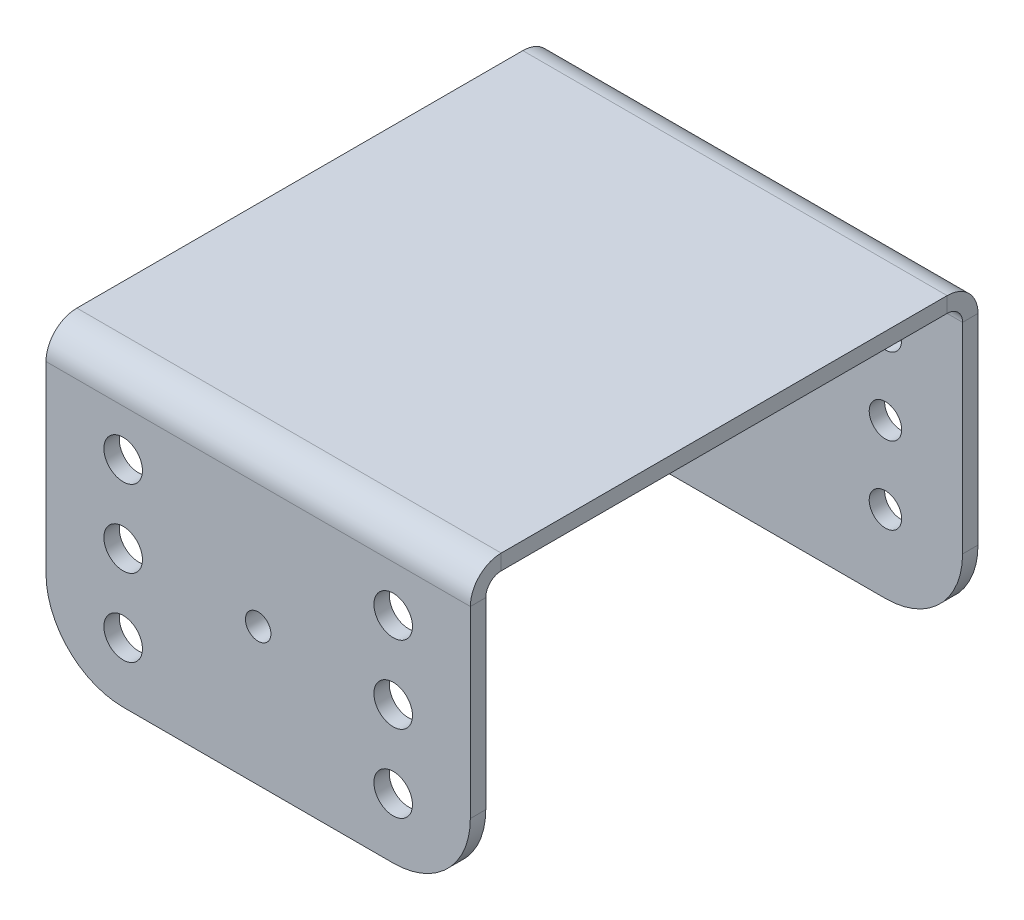
SolidWorks part; units mm, degrees
note: The reader was unsure of these and kept them because the rebuilt part matched: flange length of "边线-法兰1", "边线-法兰2".
material "1023 碳钢板 (SS)"
ref_plane "前视基准面" through (0, 0, 0) normal (0, 0, 1) x (1, 0, 0)
ref_plane "上视基准面" through (0, 0, 0) normal (0, 1, 0) x (1, 0, 0)
ref_plane "右视基准面" through (0, 0, 0) normal (1, 0, 0) x (0, 0, -1)
sketch "草图1" plane through (0, 0, 0) normal (0, 0, 1) x (1, 0, 0)
  line L0 (0, 0) -> (25062.9318, 0) construction
  line L1 (0, 0) -> (0, 25062.9318) construction
  line L3 (-27.5, 20) -> (27.5, 20)
  line L4 (-27.5, 20) -> (-27.5, -10)
  line L5 (-17.5, -20) -> (17.5, -20)
  line L6 (27.5, 20) -> (27.5, -10)
  circle A0 centre (-17.5, 10) radius 2.1
  circle A1 centre (17.5, 10) radius 2.1
  circle A2 centre (17.5, -10) radius 2.1
  circle A3 centre (-17.5, -10) radius 2.1
  arc A4 (-27.5, -10) -> (-17.5, -20) centre (-17.5, -10) ccw
  arc A5 (17.5, -20) -> (27.5, -10) centre (17.5, -10) ccw
  circle A6 centre (-17.5, 0) radius 2.1
  circle A7 centre (17.5, 0) radius 2.1
  point P19 (-27.5, -20)
  dimension "D3" = 4.2
  dimension "D4" = 10
  dimension "D5" = 10
  dimension "D6" = 10
  dimension "D7" = 4.2
  dimension "D1" = 40
  dimension "D2" = 55
base flange "基体-法兰1" sketch "草图1" thickness 2 reverse thickness direction no parameters "D1"=2
edge flange "边线-法兰1" sketch "草图8" flange angle 90 flange length 65.8 flange position material inside bend radius 2 thickness 2 relief rectangular parameters "D6"=10
sketch "草图8" plane through (0, 20, 0) normal (0, 1, 0) x (-1, 0, 0)
  line L0 (-27.5, 0) -> (27.5, 0) construction
  line L1 (-27.5, 0) -> (27.5, 0)
  line L2 (-27.5, 0) -> (-27.5, 63.8)
  line L3 (-27.5, 63.8) -> (27.5, 63.8)
  line L4 (27.5, 63.8) -> (27.5, 0)
  dimension "D1" = 63.8
bend "边线折弯1" bend radius 2 bend angle 90 parameters "D5"=1
mirror "镜向1" [suppressed] about plane through (0, 0, 0) normal (0, 1, 0)
bend "镜向折弯1" bend radius 2 bend angle 90 parameters "D5"=2
edge flange "边线-法兰2" sketch "草图11" flange angle 90 flange length 37.8 flange position material inside bend radius 2 thickness 2 relief rectangular parameters "D6"=10
sketch "草图11" plane through (0, 18, 63.8) normal (0, 0, 1) x (-1, 0, 0)
  line L2 (-27.5, 0) -> (-27.5, 25.8)
  line L3 (-17.5, 35.8) -> (17.5, 35.8)
  line L4 (27.5, 25.8) -> (27.5, 0)
  line L5 (27.5, 0) -> (-27.5, 0) construction
  line L6 (27.5, 0) -> (-27.5, 0)
  circle A0 centre (-17.5, 8) radius 2.5
  circle A1 centre (-17.5, 28) radius 2.5
  circle A2 centre (17.5, 28) radius 2.5
  circle A3 centre (17.5, 8) radius 2.5
  arc A4 (27.5, 25.8) -> (17.5, 35.8) centre (17.5, 25.8) ccw
  arc A5 (-17.5, 35.8) -> (-27.5, 25.8) centre (-17.5, 25.8) ccw
  circle A6 centre (17.5, 18) radius 2.5
  circle A7 centre (-17.5, 18) radius 2.5
  point P17 (27.5, 35.8)
  dimension "D2" = 5
  dimension "D3" = 10
  dimension "D4" = 5
  dimension "D1" = 35.8
bend "边线折弯2" bend radius 2 bend angle 90 parameters "D5"=3
sketch "草图12" plane through (0, 0, 61.8) normal (0, 0, -1) x (-1, 0, 0)
  circle A0 centre (0, 0) radius 3
  dimension "D1" = 6
extrude "凸台-拉伸1" add sketch "草图12" along normal blind 2
hole_wizard "M4 螺纹孔1" positions "草图14" profile "草图13" tap size "M4" standard "GB"
sketch "草图14" plane through (0, 0, 63.8) normal (0, 0, 1) x (1, 0, 0)
  point P0 (0, 0)
sketch "草图13" plane through (0, 0, 63.8) normal (1, 0, 0) x (0, -1, 0)
  line L0 (0, 0) -> (0, 6.9914)
  line L1 (0, 6.9914) -> (1.65, 6)
  line L2 (1.65, 6) -> (1.65, 0)
  line L5 (1.65, 0) -> (0, 0)
  line L10 (0, 6.9914) -> (-1.65, 6) construction
  line L11 (0, -6.35) -> (0, 107.95) construction
  dimension "螺纹孔钻头直径" = 3.3
  dimension "螺纹孔钻头深度" = 6
  dimension "导头角度" = 118
cosmetic thread "孔螺蚊线1"
sketch "折弯-线1" plane through (0, 0, 0) normal (0, 1, 0) x (1, 0, 0)
sketch "边界框1" plane through (0, 0, 0) normal (0, 1, 0) x (1, 0, 0)
sheet metal parameters "钣金8" thickness 2 parameters "D1"=2
flat pattern "平板型式8" [suppressed]
sketch "折弯-线2" plane through (0, 0, 0) normal (0, 1, 0) x (1, 0, 0)
sketch "边界框2" [suppressed] plane through (0, 0, 0) normal (0, 1, 0) x (1, 0, 0)
sheet metal parameters "钣金9" thickness 2 parameters "D1"=2
flat pattern "平板型式8" [suppressed]
sketch "折弯-线2" plane through (0, 0, 0) normal (0, 1, 0) x (1, 0, 0)
sketch "边界框2" [suppressed] plane through (0, 0, 0) normal (0, 1, 0) x (1, 0, 0)
bend of the flat pattern "展开-<边线折弯1>1"
sheet metal parameters "钣金10" thickness 2 parameters "D1"=2
flat pattern "平板型式8" [suppressed]
sketch "折弯-线2" plane through (0, 0, 0) normal (0, 1, 0) x (1, 0, 0)
sketch "边界框2" [suppressed] plane through (0, 0, 0) normal (0, 1, 0) x (1, 0, 0)
bend of the flat pattern "展开-<边线折弯1>1"
bend of the flat pattern "展开-<镜向折弯1>1"
sheet metal parameters "钣金11" thickness 2 parameters "D1"=2
flat pattern "平板型式8" [suppressed]
sketch "折弯-线2" plane through (0, 0, 0) normal (0, 1, 0) x (1, 0, 0)
sketch "边界框2" [suppressed] plane through (0, 0, 0) normal (0, 1, 0) x (1, 0, 0)
bend of the flat pattern "展开-<边线折弯1>1"
bend of the flat pattern "展开-<边线折弯2>1"
sheet metal parameters "钣金12" thickness 2 parameters "D1"=2
flat pattern "平板型式8" [suppressed]
sketch "折弯-线2" plane through (0, 0, 0) normal (0, 1, 0) x (1, 0, 0)
sketch "边界框2" [suppressed] plane through (0, 0, 0) normal (0, 1, 0) x (1, 0, 0)
bend of the flat pattern "展开-<边线折弯1>1"
bend of the flat pattern "展开-<边线折弯2>1"
sheet metal parameters "钣金13" thickness 2 parameters "D1"=2
flat pattern "平板型式8" [suppressed]
sketch "折弯-线2" plane through (0, 0, 0) normal (0, 1, 0) x (1, 0, 0)
sketch "边界框2" [suppressed] plane through (0, 0, 0) normal (0, 1, 0) x (1, 0, 0)
bend of the flat pattern "展开-<边线折弯1>1"
bend of the flat pattern "展开-<边线折弯2>1"
